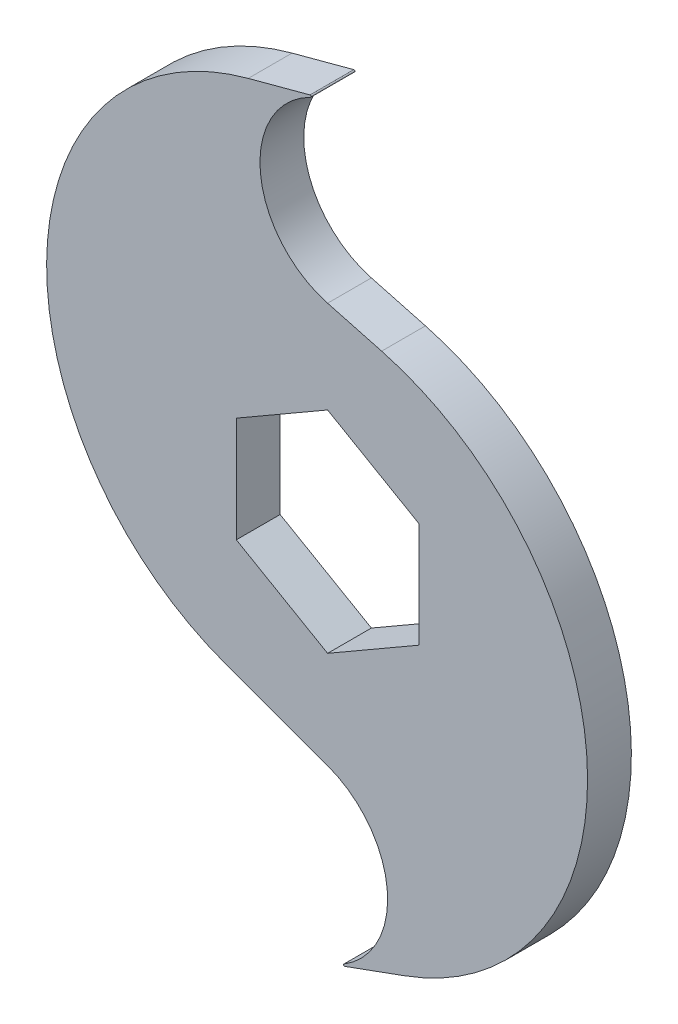
SolidWorks part; units mm, degrees
ref_plane "Front Plane" through (0, 0, 0) normal (0, 0, 1) x (1, 0, 0)
ref_plane "Top Plane" through (0, 0, 0) normal (0, 1, 0) x (1, 0, 0)
ref_plane "Right Plane" through (0, 0, 0) normal (1, 0, 0) x (0, 0, -1)
sketch "Sketch1" plane through (0, 0, 0) normal (0, 0, 1) x (1, 0, 0)
  line L0 (0, 52.07) -> (-11.0405, 49.1117)
  line L1 (0, 52.07) -> (0, 0) construction
  line L2 (0, -52.07) -> (10.7407, -48.1607)
  line L3 (0, 0) -> (0, -52.07) construction
  line L5 (0, 14.6647) -> (-12.7, 7.3323)
  line L6 (-12.7, 7.3323) -> (-12.7, -7.3323)
  line L7 (-12.7, -7.3323) -> (0, -14.6647)
  line L8 (0, -14.6647) -> (12.7, -7.3323)
  line L9 (12.7, -7.3323) -> (12.7, 7.3323)
  line L10 (12.7, 7.3323) -> (0, 14.6647)
  line L11 (0, 27.5355) -> (7.5237, 25.5195)
  line L12 (0, -28.2018) -> (-14.1906, -23.0368)
  circle A0 centre (0, 0) radius 52.07 construction
  arc A1 (0, 52.07) -> (0, 27.5355) centre (3.287, 39.8027) ccw
  arc A3 (0, -52.07) -> (0, -28.2018) centre (-4.3437, -40.1359) ccw
  arc A4 (10.7407, -48.1607) -> (7.5237, 25.5195) centre (-2.4834, -11.8278) ccw
  arc A5 (-11.0405, 49.1117) -> (-14.1906, -23.0368) centre (-1.2414, 12.5408) ccw
  circle A6 centre (0, 0) radius 12.7 construction
  dimension "D4" = 70
  dimension "D5" = 25.4
  dimension "D1" = 104.14
  dimension "D6" = 12.7
  dimension "D2" = 11.43
  dimension "D3" = 75
extrude "Boss-Extrude1" add sketch "Sketch1" along normal mid plane 6.096
fillet "Fillet1" radius 0.127 2 edges at (0, 52.07, 0) (0, -52.07, 0)
